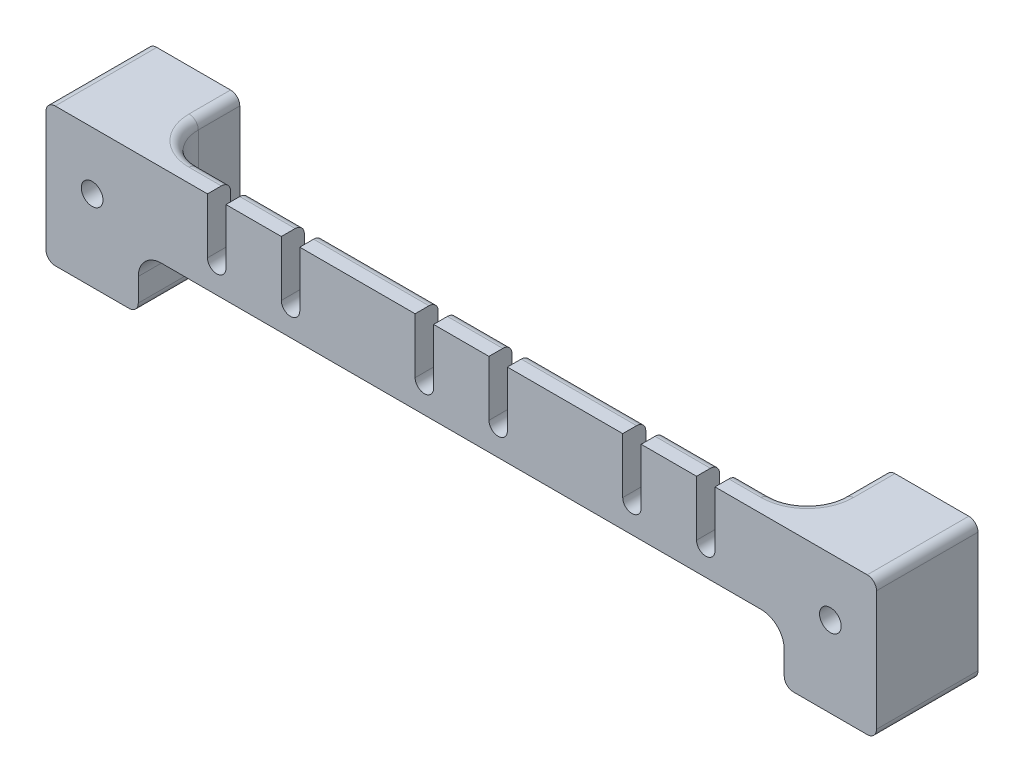
SolidWorks part; units mm, degrees
material "ABS"
ref_plane "Front Plane" through (0, 0, 0) normal (0, 0, 1) x (1, 0, 0)
ref_plane "Top Plane" through (0, 0, 0) normal (0, 1, 0) x (1, 0, 0)
ref_plane "Right Plane" through (0, 0, 0) normal (1, 0, 0) x (0, 0, -1)
sketch "Sketch1" plane through (0, 0, 0) normal (0, 0, 1) x (1, 0, 0)
  line L1 (0, 0) -> (180, 0)
  line L2 (0, 0) -> (0, 30)
  line L3 (0, 30) -> (180, 30)
  line L4 (180, 0) -> (180, 30)
  circle A0 centre (10, 17.5) radius 2.35
  circle A1 centre (170, 17.5) radius 2.35
  dimension "D2" = 4.7
  dimension "D1" = 180
  dimension "D3" = 30
  dimension "D4" = 160
  dimension "D5" = 10
  dimension "D6" = 12.5
extrude "Boss-Extrude1" add sketch "Sketch1" along normal blind 22
sketch "Sketch2" plane through (0, 30, 0) normal (0, 1, 0) x (1, 0, 0)
  line L0 (180, 0) -> (0, 0) construction
  line L1 (160, 0) -> (20, 0)
  line L2 (160, 0) -> (160, -17)
  line L3 (160, -17) -> (20, -17)
  line L4 (20, 0) -> (20, -17)
  line L5 (180, -22) -> (180, 0) construction
  line L6 (0, -22) -> (0, 0) construction
  dimension "D1" = 20
  dimension "D2" = 20
  dimension "D3" = 17
extrude "Cut-Extrude1" cut sketch "Sketch2" against normal blind 30
sketch "Sketch3" plane through (0, 0, 22) normal (0, 0, 1) x (1, 0, 0)
  line L1 (20, 0) -> (160, 0)
  line L2 (20, 0) -> (20, 12)
  line L3 (20, 12) -> (160, 12)
  line L4 (160, 0) -> (160, 12)
  line L5 (0, 30) -> (0, 0) construction
  line L6 (180, 0) -> (180, 30) construction
  line L7 (0, 0) -> (180, 0) construction
  dimension "D1" = 20
  dimension "D2" = 20
  dimension "D3" = 12
extrude "Cut-Extrude2" cut sketch "Sketch3" against normal blind 22
sketch "Sketch4" plane through (0, 0, 22) normal (0, 0, 1) x (1, 0, 0)
  line L3 (143, 18) -> (143, 30) construction
  line L4 (141, 18) -> (141, 30)
  line L5 (145, 18) -> (145, 30)
  line L7 (160, 12) -> (20, 12) construction
  line L8 (180, 0) -> (180, 30) construction
  line L9 (98, 18) -> (98, 30) construction
  line L10 (96, 18) -> (96, 30)
  line L11 (100, 18) -> (100, 30)
  line L12 (53, 18) -> (53, 30) construction
  line L13 (51, 18) -> (51, 30)
  line L14 (55, 18) -> (55, 30)
  line L15 (37, 18) -> (37, 30) construction
  line L16 (35, 18) -> (35, 30)
  line L17 (39, 18) -> (39, 30)
  line L18 (0, 30) -> (0, 0) construction
  line L19 (82, 18) -> (82, 30) construction
  line L20 (80, 18) -> (80, 30)
  line L21 (84, 18) -> (84, 30)
  line L22 (127, 18) -> (127, 30) construction
  line L23 (125, 18) -> (125, 30)
  line L24 (129, 18) -> (129, 30)
  arc A3 (141, 18) -> (145, 18) centre (143, 18) ccw
  arc A4 (145, 30) -> (141, 30) centre (143, 30) ccw
  arc A5 (96, 18) -> (100, 18) centre (98, 18) ccw
  arc A6 (100, 30) -> (96, 30) centre (98, 30) ccw
  arc A7 (51, 18) -> (55, 18) centre (53, 18) ccw
  arc A8 (55, 30) -> (51, 30) centre (53, 30) ccw
  arc A9 (35, 18) -> (39, 18) centre (37, 18) ccw
  arc A10 (39, 30) -> (35, 30) centre (37, 30) ccw
  arc A11 (80, 18) -> (84, 18) centre (82, 18) ccw
  arc A12 (84, 30) -> (80, 30) centre (82, 30) ccw
  arc A13 (125, 18) -> (129, 18) centre (127, 18) ccw
  arc A14 (129, 30) -> (125, 30) centre (127, 30) ccw
  point P7 (143, 24)
  point P8 (98, 24)
  point P20 (53, 24)
  point P27 (37, 24)
  point P37 (82, 24)
  point P44 (127, 24)
  dimension "D1" = 12
  dimension "D3" = 4
  dimension "D4" = 12
  dimension "D8" = 12
  dimension "D2" = 37
  dimension "D5" = 3
  dimension "D6" = 45
  dimension "D7" = 37
  dimension "D9" = 4
  dimension "D10" = 12
  dimension "D12" = 45
  dimension "D11" = 3
extrude "Cut-Extrude3" cut sketch "Sketch4" against normal blind 48
fillet "Fillet1" radius 8 2 edges at (160, 21, 17) (20, 21, 17)
fillet "Fillet2" radius 5 2 edges at (20, 12, 15.5) (160, 12, 15.5)
fillet "Fillet3" radius 2 5 edges at (158.1848, 10.8545, 14.0742) (153.5281, 12, 16.8527) (90, 12, 17) (26.4719, 12, 16.8527) (21.8152, 10.8545, 14.0742)
fillet "Fillet4" radius 2 17 edges at (20, 30, 4.5) (22.3431, 30, 14.6569) (31.5, 30, 17) (148.5, 30, 17) (157.6569, 30, 14.6569) (160, 30, 4.5) (180, 30, 11) (0, 30, 11) (0, 0, 11) (180, 0, 11) (160, 0, 11) (20, 0, 11) (135, 30, 17) (112.5, 30, 17) (90, 30, 17) (67.5, 30, 17) (45, 30, 17)
